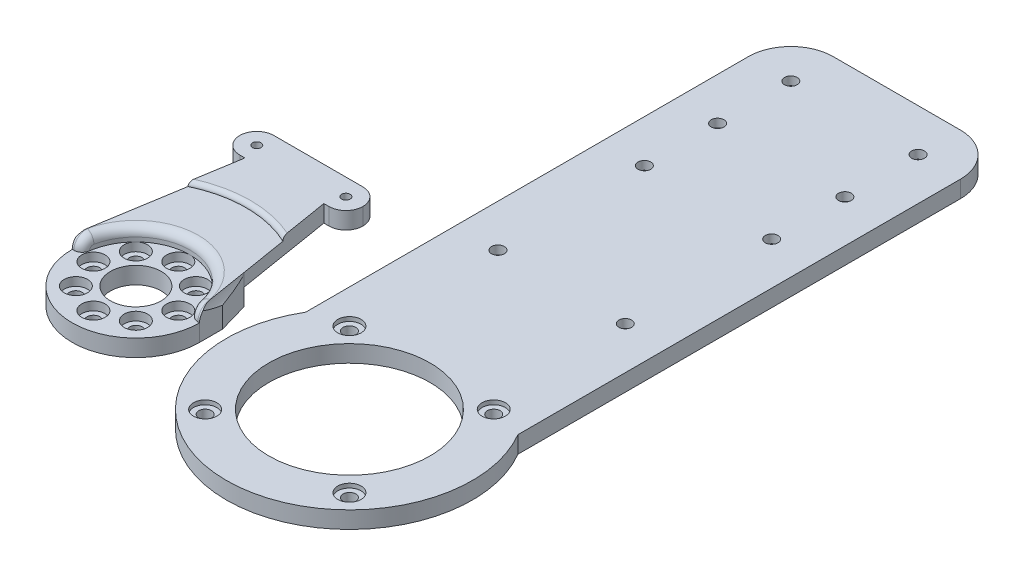
SolidWorks part; units mm, degrees
ref_plane "前视基准面" through (0, 0, 0) normal (0, 0, 1) x (1, 0, 0)
ref_plane "上视基准面" through (0, 0, 0) normal (0, 1, 0) x (1, 0, 0)
ref_plane "右视基准面" through (0, 0, 0) normal (1, 0, 0) x (0, 0, -1)
sketch "草图1" plane through (0, 0, 0) normal (0, 1, 0) x (1, 0, 0)
  circle A0 centre (0, 0) radius 15
  circle A1 centre (0, 0) radius 6
  dimension "D1" = 30
  dimension "D2" = 12
extrude "凸台-拉伸1" add sketch "草图1" along normal blind 2
sketch "草图2" plane through (0, 2, 0) normal (0, 1, 0) x (1, 0, 0)
  circle A0 centre (10, 0) radius 1.5
  dimension "D2" = 3
extrude "切除-拉伸1" cut sketch "草图2" against normal blind 2
pattern_circular "阵列(圆周)1" count 8 over 360 about axis through (0, 2, 0) along (0, -1, 0) of "切除-拉伸1"
sketch "草图3" plane through (0, 2, 0) normal (0, 1, 0) x (1, 0, 0)
  circle A1 centre (0, 0) radius 15
extrude "凸台-拉伸2" add sketch "草图3" along normal blind 2
sketch "草图4" plane through (0, 2, 0) normal (0, -1, 0) x (1, 0, 0)
  circle A0 centre (7.0711, 7.0711) radius 2.75
  dimension "D1" = 5.5
extrude "切除-拉伸2" cut sketch "草图4" against normal blind 2
pattern_circular "阵列(圆周)2" count 8 over 360 about axis through (0, 2, 0) along (0, -1, 0) of "切除-拉伸2"
sketch "草图5" plane through (0, 2, 0) normal (0, -1, 0) x (1, 0, 0)
  circle A0 centre (0, 0) radius 6
extrude "切除-拉伸3" cut sketch "草图5" against normal blind 2
sketch "草图8" plane through (0, 4, 0) normal (0, 1, 0) x (1, 0, 0)
  line L0 (-15, 0) -> (-12.75, 0)
  line L1 (12.75, 0) -> (15, 0)
  line L2 (0, 43) -> (-8, 43)
  line L3 (0, 43) -> (8, 43)
  line L4 (-15, 0) -> (-8, 43)
  line L5 (15, 0) -> (8, 43)
  circle A0 centre (0, 0) radius 15 construction
  arc A1 (12.75, 0) -> (-12.75, 0) centre (0, 0) ccw
  circle A2 centre (10, 0) radius 2.75 construction
  circle A3 centre (10, 0) radius 2.75 construction
  circle A4 centre (-10, 0) radius 2.75 construction
  dimension "D3" = 8
  dimension "D4" = 8
sketch "草图9" plane through (0, 0, 0) normal (0, -1, 0) x (1, 0, 0)
  line L0 (15, 0) -> (8, -43) construction
  line L1 (-15, 0) -> (-8, -43) construction
  line L2 (-15, 0) -> (-15, -5.4278)
  line L3 (-15, -5.4278) -> (-12.9678, -12.4834)
  line L4 (15, 0) -> (15, -5.4278)
  line L5 (15, -5.4278) -> (12.9678, -12.4834)
  arc A0 (-15, 0) -> (15, 0) centre (0, 0) ccw
  arc A1 (-12.9678, -12.4834) -> (12.9678, -12.4834) centre (0, 0) ccw
  dimension "D1" = 18
extrude "凸台-拉伸3" add sketch "草图9" against normal blind 4
extrude "凸台-拉伸4" add sketch "草图8" along normal blind 3
fillet "圆角1" radius 3 2 edges at (13.875, 7, 0) (-13.875, 7, 0)
fillet "圆角2" radius 2 3 edges at (-12.6981, 6.3608, -1.1489) (12.7331, 5.8732, -0.6567) (0, 7, -12.75)
fillet "圆角4" radius 3 2 edges at (-13.9839, 4, -6.2417) (13.9839, 4, -6.2417)
sketch "草图11" plane through (0, 7, 0) normal (0, 1, 0) x (1, 0, 0)
  line L3 (-8, 43) -> (-12.9678, 12.4834) construction
  line L4 (12.9678, 12.4834) -> (8, 43) construction
  line L5 (11.1786, 23.4742) -> (8, 43)
  line L6 (8, 43) -> (-8, 43)
  line L7 (-8, 43) -> (-11.1786, 23.4742)
  arc A1 (-11.1786, 23.4742) -> (11.1786, 23.4742) centre (0, 0) cw
extrude "凸台-拉伸5" add sketch "草图11" along normal blind 1
sketch "草图12" plane through (0, 4, 0) normal (0, -1, 0) x (1, 0, 0)
  line L5 (0, -36.6329) -> (-2.05, -37.8164)
  line L6 (-2.05, -37.8164) -> (-2.05, -40.1836)
  line L7 (-2.05, -40.1836) -> (0, -41.3671)
  line L8 (0, -41.3671) -> (2.05, -40.1836)
  line L9 (2.05, -40.1836) -> (2.05, -37.8164)
  line L10 (2.05, -37.8164) -> (0, -36.6329)
  line L13 (-5, -28.6329) -> (-7.05, -29.8164)
  line L14 (-7.05, -29.8164) -> (-7.05, -32.1836)
  line L15 (-7.05, -32.1836) -> (-5, -33.3671)
  line L16 (-5, -33.3671) -> (-2.95, -32.1836)
  line L17 (-2.95, -32.1836) -> (-2.95, -29.8164)
  line L18 (-2.95, -29.8164) -> (-5, -28.6329)
  line L19 (5, -28.6329) -> (2.95, -29.8164)
  line L20 (2.95, -29.8164) -> (2.95, -32.1836)
  line L21 (2.95, -32.1836) -> (5, -33.3671)
  line L22 (5, -33.3671) -> (7.05, -32.1836)
  line L23 (7.05, -32.1836) -> (7.05, -29.8164)
  line L24 (7.05, -29.8164) -> (5, -28.6329)
  circle A0 centre (0, -39) radius 2.05 construction
  circle A1 centre (-5, -31) radius 2.05 construction
  circle A2 centre (5, -31) radius 2.05 construction
  dimension "D2" = 4.1
  dimension "D5" = 4.1
  dimension "D6" = 4.1
extrude "切除-拉伸4" cut sketch "草图12" against normal blind 2
sketch "草图13" plane through (0, 6, 0) normal (0, -1, 0) x (1, 0, 0)
  circle A0 centre (5, -31) radius 1
  circle A1 centre (-5, -31) radius 1
  circle A2 centre (0, -39) radius 1
  dimension "D1" = 2
  dimension "D2" = 2
  dimension "D3" = 2
extrude "切除-拉伸5" cut sketch "草图13" against normal blind 2
fillet "圆角6" radius 1 1 edges at (0, 8, -26)
fillet "圆角7" radius 1 18 edges at (-1.025, 6, -40.7754) (-2.05, 6, -39) (-1.025, 6, -37.2246) (1.025, 6, -37.2246) (2.05, 6, -39) (1.025, 6, -40.7754) (-2.95, 6, -31) (-3.975, 6, -32.7754) (-6.025, 6, -32.7754) (-7.05, 6, -31) (-3.975, 6, -29.2246) (-6.025, 6, -29.2246) (7.05, 6, -31) (6.025, 6, -32.7754) (3.975, 6, -32.7754) (2.95, 6, -31) (3.975, 6, -29.2246) (6.025, 6, -29.2246)
sketch "草图14" plane through (0, 8, 0) normal (0, 1, 0) x (1, 0, 0)
  circle A0 centre (5, 31) radius 2.3958
  circle A1 centre (-5, 31) radius 3.3415
  circle A2 centre (0, 39) radius 3.655
extrude "凸台-拉伸6" add sketch "草图14" against normal blind 4
sketch "草图15" plane through (0, 8, 0) normal (0, 1, 0) x (1, 0, 0)
  line L3 (-12.5, 43) -> (12.5, 43)
  line L4 (-12.5, 43) -> (-12.5, 35)
  line L5 (12.5, 43) -> (12.5, 35)
  line L6 (-12.5, 35) -> (12.5, 35)
  line L7 (-12.5, 43) -> (12.5, 35) construction
  line L8 (12.5, 43) -> (-12.5, 35) construction
extrude "凸台-拉伸7" add sketch "草图15" against normal blind 4
sketch "草图16" plane through (0, 8, 0) normal (0, 1, 0) x (1, 0, 0)
  circle A0 centre (10.5, 39) radius 1
  circle A1 centre (-10.5, 39) radius 1
  dimension "D4" = 2
  dimension "D5" = 2
extrude "切除-拉伸6" cut sketch "草图16" against normal blind 4
sketch "草图17" plane through (0, 4, 0) normal (0, -1, 0) x (1, 0, 0)
  line L1 (10.5, -41.3671) -> (12.55, -40.1836)
  line L2 (12.55, -40.1836) -> (12.55, -37.8164)
  line L3 (12.55, -37.8164) -> (10.5, -36.6329)
  line L4 (10.5, -36.6329) -> (8.45, -37.8164)
  line L5 (8.45, -37.8164) -> (8.45, -40.1836)
  line L6 (8.45, -40.1836) -> (10.5, -41.3671)
  line L7 (-10.5, -41.3671) -> (-8.45, -40.1836)
  line L8 (-8.45, -40.1836) -> (-8.45, -37.8164)
  line L9 (-8.45, -37.8164) -> (-10.5, -36.6329)
  line L10 (-10.5, -36.6329) -> (-12.55, -37.8164)
  line L11 (-12.55, -37.8164) -> (-12.55, -40.1836)
  line L12 (-12.55, -40.1836) -> (-10.5, -41.3671)
  circle A0 centre (10.5, -39) radius 2.05 construction
  circle A1 centre (-10.5, -39) radius 2.05 construction
  dimension "D1" = 4.1
  dimension "D2" = 4.1
extrude "切除-拉伸7" cut sketch "草图17" against normal blind 2.5
sketch "草图18" plane through (-12.5, 0, 0) normal (-1, 0, 0) x (0, 0, 1)
  line L0 (-43, 8) -> (-43, 4)
  line L1 (-43, 8) -> (-35, 8)
  line L2 (-43, 4) -> (-35, 4)
  line L3 (-35, 8) -> (-35, 4)
  dimension "D1" = 8
extrude "凸台-拉伸8" add sketch "草图18" along normal blind 2
sketch "草图19" plane through (12.5, 0, 0) normal (1, 0, 0) x (0, 0, -1)
  line L0 (35, 4) -> (35, 8)
  line L1 (35, 4) -> (43, 4)
  line L2 (35, 8) -> (43, 8)
  line L3 (43, 4) -> (43, 8)
  dimension "D1" = 8
extrude "凸台-拉伸9" add sketch "草图19" along normal blind 2
fillet "圆角9" radius 1 12 edges at (11.5, 6.5, -37.2102) (12.5, 6.5, -39) (11.5, 6.5, -40.7898) (9.475, 6.5, -40.7754) (8.45, 6.5, -39) (9.475, 6.5, -37.2246) (-9.475, 6.5, -40.7754) (-8.45, 6.5, -39) (-9.475, 6.5, -37.2246) (-11.5, 6.5, -37.2102) (-12.5, 6.5, -39) (-11.5, 6.5, -40.7898)
fillet "圆角10" radius 4 4 edges at (14.5, 6, -35) (14.5, 6, -43) (-14.5, 6, -35) (-14.5, 6, -43)
sketch "草图20" plane through (0, 0, 0) normal (0, 1, 0) x (1, 0, 0)
  circle A0 centre (50.3278, 0) radius 19
  circle A1 centre (50.3278, 0) radius 29
  circle A2 centre (33.3278, 17) radius 1.5
  circle A3 centre (67.3278, 17) radius 1.5
  circle A4 centre (67.3278, -17) radius 1.5
  circle A5 centre (33.3278, -17) radius 1.5
  dimension "D1" = 38
  dimension "D2" = 10
  dimension "D9" = 3
  dimension "D10" = 3
  dimension "D11" = 3
  dimension "D12" = 3
  dimension "D5" = 34
  dimension "D7" = 34
  dimension "D8" = 34
extrude "凸台-拉伸11" add sketch "草图20" along normal blind 4 separate body
sketch "草图23" plane through (0, 4, 0) normal (0, 1, 0) x (1, 0, 0)
  circle A0 centre (33.3278, 17) radius 2.75
  dimension "D1" = 5.5
extrude "切除-拉伸9" cut sketch "草图23" against normal blind 1
pattern_circular "阵列(圆周)5" count 4 over 360 about axis through (50.3278, 4, 0) along (0, -1, 0) of "切除-拉伸9"
sketch "草图24" plane through (0, 0, 0) normal (0, 1, 0) x (1, 0, 0)
  line L0 (25.3278, 129) -> (25.3278, 13.9125)
  line L1 (75.3278, 129) -> (75.3278, 13.9125)
  line L2 (25.3278, 13.9125) -> (31.7041, 20.2888)
  line L3 (31.7041, 20.2888) -> (45.6953, 26.2153)
  line L4 (45.6953, 26.2153) -> (61.6544, 25.3078)
  line L5 (61.6544, 25.3078) -> (69.4628, 20.2888)
  line L6 (69.4628, 20.2888) -> (75.3278, 13.9125)
  line L8 (50.3278, 129) -> (25.3278, 129)
  line L9 (50.3278, 129) -> (75.3278, 129)
  circle A0 centre (35.3278, 50) radius 1.5
  circle A1 centre (65.3278, 50) radius 1.5
  circle A2 centre (35.3278, 119) radius 1.5
  circle A3 centre (65.3278, 119) radius 1.5
  dimension "D7" = 3
  dimension "D8" = 3
  dimension "D9" = 3
  dimension "D10" = 3
  dimension "D11" = 25
  dimension "D12" = 25
extrude "凸台-拉伸12" add sketch "草图24" along normal blind 4
sketch "草图25" plane through (0, 4, 0) normal (0, 1, 0) x (1, 0, 0)
  circle A0 centre (35.3278, 84.5) radius 1.5
  circle A1 centre (65.3278, 84.5) radius 1.5
  circle A2 centre (35.3278, 101.75) radius 1.5
  circle A3 centre (65.3278, 101.75) radius 1.5
  dimension "D1" = 3
  dimension "D2" = 3
  dimension "D3" = 3
  dimension "D4" = 3
extrude "切除-拉伸10" cut sketch "草图25" against normal blind 4
sketch "草图27" plane through (0, 0, 0) normal (0, -1, 0) x (1, 0, 0)
  line L1 (35.3278, -53.2332) -> (38.1278, -51.6166)
  line L2 (38.1278, -51.6166) -> (38.1278, -48.3834)
  line L3 (38.1278, -48.3834) -> (35.3278, -46.7668)
  line L4 (35.3278, -46.7668) -> (32.5278, -48.3834)
  line L5 (32.5278, -48.3834) -> (32.5278, -51.6166)
  line L6 (32.5278, -51.6166) -> (35.3278, -53.2332)
  line L7 (65.3278, -53.2332) -> (68.1278, -51.6166)
  line L8 (68.1278, -51.6166) -> (68.1278, -48.3834)
  line L9 (68.1278, -48.3834) -> (65.3278, -46.7668)
  line L10 (65.3278, -46.7668) -> (62.5278, -48.3834)
  line L11 (62.5278, -48.3834) -> (62.5278, -51.6166)
  line L12 (62.5278, -51.6166) -> (65.3278, -53.2332)
  line L13 (35.3278, -87.7332) -> (38.1278, -86.1166)
  line L14 (38.1278, -86.1166) -> (38.1278, -82.8834)
  line L15 (38.1278, -82.8834) -> (35.3278, -81.2668)
  line L16 (35.3278, -81.2668) -> (32.5278, -82.8834)
  line L17 (32.5278, -82.8834) -> (32.5278, -86.1166)
  line L18 (32.5278, -86.1166) -> (35.3278, -87.7332)
  line L19 (65.3278, -87.7332) -> (68.1278, -86.1166)
  line L20 (68.1278, -86.1166) -> (68.1278, -82.8834)
  line L21 (68.1278, -82.8834) -> (65.3278, -81.2668)
  line L22 (65.3278, -81.2668) -> (62.5278, -82.8834)
  line L23 (62.5278, -82.8834) -> (62.5278, -86.1166)
  line L24 (62.5278, -86.1166) -> (65.3278, -87.7332)
  line L25 (35.3278, -104.9832) -> (38.1278, -103.3666)
  line L26 (38.1278, -103.3666) -> (38.1278, -100.1334)
  line L27 (38.1278, -100.1334) -> (35.3278, -98.5168)
  line L28 (35.3278, -98.5168) -> (32.5278, -100.1334)
  line L29 (32.5278, -100.1334) -> (32.5278, -103.3666)
  line L30 (32.5278, -103.3666) -> (35.3278, -104.9832)
  line L31 (65.3278, -104.9832) -> (68.1278, -103.3666)
  line L32 (68.1278, -103.3666) -> (68.1278, -100.1334)
  line L33 (68.1278, -100.1334) -> (65.3278, -98.5168)
  line L34 (65.3278, -98.5168) -> (62.5278, -100.1334)
  line L35 (62.5278, -100.1334) -> (62.5278, -103.3666)
  line L36 (62.5278, -103.3666) -> (65.3278, -104.9832)
  line L37 (35.3278, -122.2332) -> (38.1278, -120.6166)
  line L38 (38.1278, -120.6166) -> (38.1278, -117.3834)
  line L39 (38.1278, -117.3834) -> (35.3278, -115.7668)
  line L40 (35.3278, -115.7668) -> (32.5278, -117.3834)
  line L41 (32.5278, -117.3834) -> (32.5278, -120.6166)
  line L42 (32.5278, -120.6166) -> (35.3278, -122.2332)
  line L43 (65.3278, -122.2332) -> (68.1278, -120.6166)
  line L44 (68.1278, -120.6166) -> (68.1278, -117.3834)
  line L45 (68.1278, -117.3834) -> (65.3278, -115.7668)
  line L46 (65.3278, -115.7668) -> (62.5278, -117.3834)
  line L47 (62.5278, -117.3834) -> (62.5278, -120.6166)
  line L48 (62.5278, -120.6166) -> (65.3278, -122.2332)
  circle A0 centre (35.3278, -50) radius 2.8 construction
  circle A1 centre (65.3278, -50) radius 2.8 construction
  circle A2 centre (35.3278, -84.5) radius 2.8 construction
  circle A3 centre (65.3278, -84.5) radius 2.8 construction
  circle A4 centre (35.3278, -101.75) radius 2.8 construction
  circle A5 centre (65.3278, -101.75) radius 2.8 construction
  circle A6 centre (35.3278, -119) radius 2.8 construction
  circle A7 centre (65.3278, -119) radius 2.8 construction
  dimension "D1" = 5.6
  dimension "D2" = 5.6
  dimension "D3" = 5.6
  dimension "D4" = 5.6
  dimension "D5" = 5.6
  dimension "D6" = 5.6
  dimension "D7" = 5.6
  dimension "D8" = 5.6
extrude "切除-拉伸11" cut sketch "草图27" against normal blind 2
fillet "圆角11" radius 10 2 edges at (75.3278, 2, -129) (25.3278, 2, -129)
